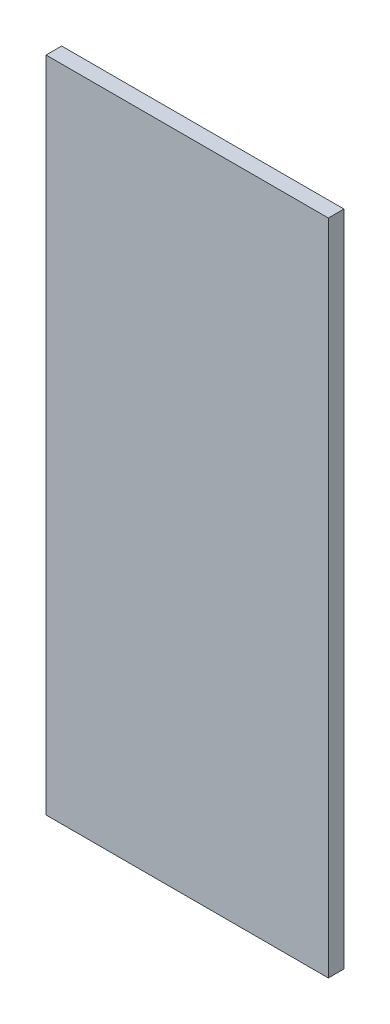
SolidWorks part; units mm, degrees
material "Perspex (TM) GS Acrylic Cast Sheet"
ref_plane "Front Plane" through (0, 0, 0) normal (0, 0, 1) x (1, 0, 0)
ref_plane "Top Plane" through (0, 0, 0) normal (0, 1, 0) x (1, 0, 0)
ref_plane "Right Plane" through (0, 0, 0) normal (1, 0, 0) x (0, 0, -1)
sketch "Sketch1" plane through (0, 0, 0) normal (0, 0, 1) x (1, 0, 0)
  line L1 (-81.5, -190) -> (81.5, -190)
  line L2 (-81.5, -190) -> (-81.5, 190)
  line L3 (-81.5, 190) -> (81.5, 190)
  line L4 (81.5, -190) -> (81.5, 190)
  line L5 (-81.5, -190) -> (81.5, 190) construction
  line L6 (-81.5, 190) -> (81.5, -190) construction
  point P0 (0, 0)
  dimension "D1" = 163
  dimension "D2" = 380
extrude "Boss-Extrude1" add sketch "Sketch1" along normal blind 9
equation "\"PCLength\"= 145mm'Length across I/O from PS to GPU"
equation "\"PCWidth\"= 340mm'Distance of longest part parallel to GPU(ussually GPU)"
equation "\"PCHeight\"= 180mm'Tallest point with mobo laying flat"
equation "\"WallThickness\"= 9mm'Thickness of each outer tank wall"
equation "\"ThermoBarrierThickness\"= 6mm'Thickness of barrier between hot side and cold side"
equation "\"HotSideGap\"= 36mm'Space in the hot side for a pump"
equation "\"PCClearance\"= 40mm'Clearance from top of tank to top of PC"
equation "\"RadiatorHeight\"= 277.37mm'Final Height from ground of radiators"
equation "\"D1@Sketch1\"=\"PCLength\" + (2 * \"WallThickness\")"
equation "\"D2@Sketch1\"=\"PCWidth\" + \"PCClearance\""
equation "\"D1@Boss-Extrude1\"=\"WallThickness\""
